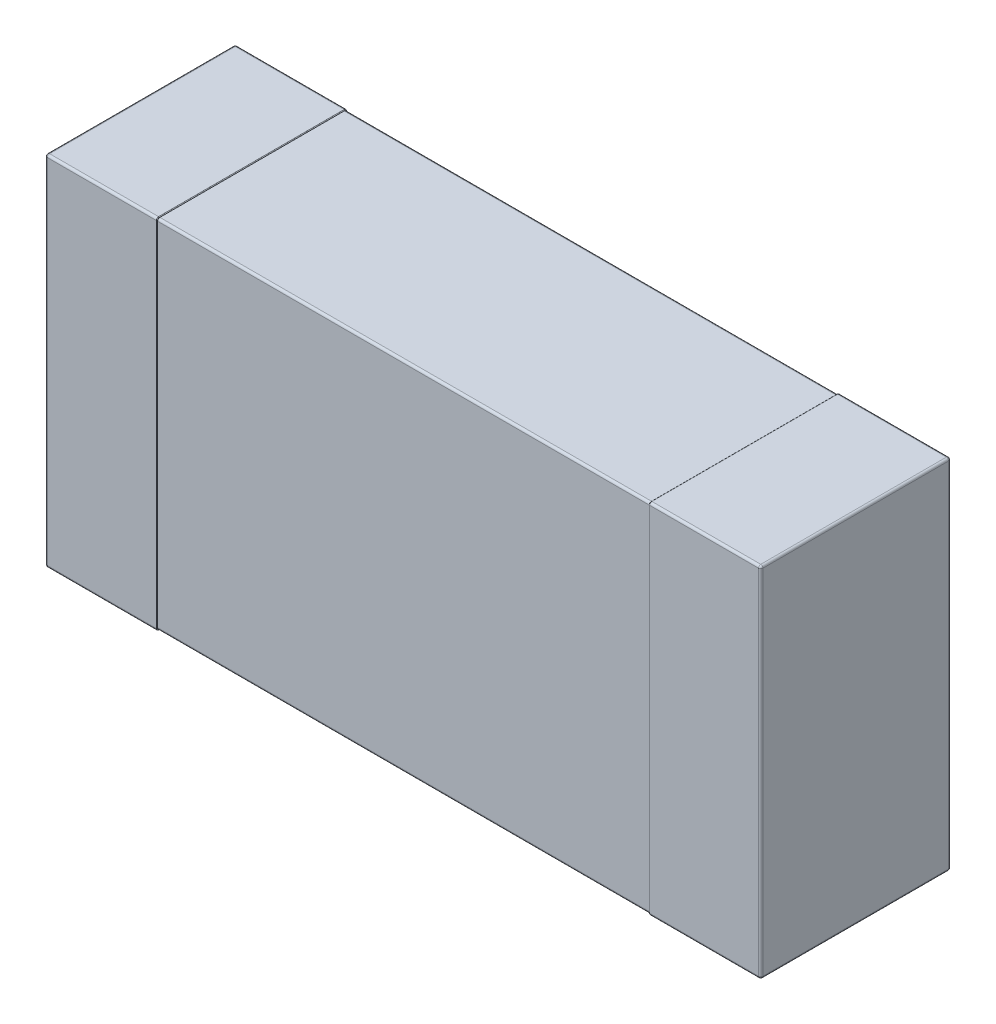
SolidWorks part; units mm, degrees
ref_plane "Top Plane" through (0, 0, 0) normal (0, 0, 1) x (1, 0, 0)
ref_plane "Front Plane" through (0, 0, 0) normal (0, 1, 0) x (1, 0, 0)
ref_plane "Side Plane" through (0, 0, 0) normal (1, 0, 0) x (0, 0, -1)
sketch "Sketch1" plane through (0, 0, 0) normal (0, 0, 1) x (1, 0, 0)
  line L1 (-1.6, 0.8) -> (1.6, 0.8)
  line L2 (-1.6, 0.8) -> (-1.6, -0.8)
  line L3 (-1.6, -0.8) -> (1.6, -0.8)
  line L4 (1.6, 0.8) -> (1.6, -0.8)
  dimension "D1" = 3.2
  dimension "D2" = 1.6
  dimension "D3" = 1.6
  dimension "D4" = 0.8
extrude "All body" add sketch "Sketch1" along normal blind 0.85
sketch "Sketch2" plane through (0, 0, 0) normal (1, 0, 0) x (0, 0, -1)
  line L14 (-0.003, 0.797) -> (-0.847, 0.797)
  line L15 (-0.003, -0.797) -> (-0.003, 0.797)
  line L16 (-0.847, -0.797) -> (-0.003, -0.797)
  line L17 (-0.847, 0.797) -> (-0.847, -0.797)
  line L18 (-0.003, 0.797) -> (-0.847, 0.797)
  line L19 (-0.003, -0.797) -> (-0.003, 0.797)
  line L20 (-0.847, -0.797) -> (-0.003, -0.797)
  line L21 (-0.847, 0.797) -> (-0.847, -0.797)
  dimension "D1" = 0.003
extrude "Cut out the body for pin" cut sketch "Sketch2" against normal blind 1.1 and the other way blind 1.1 flip side to cut
fillet "Body fillet" radius 0.01 4 edges at (0, 0.797, 0.003) (0, 0.797, 0.847) (0, -0.797, 0.003) (0, -0.797, 0.847)
fillet "Pin fillet a" radius 0.01 16 edges at (1.6, -0.8, 0.425) (1.6, 0, 0.85) (1.6, 0.8, 0.425) (1.6, 0, 0) (-1.6, 0.8, 0.425) (-1.6, 0, 0.85) (-1.6, -0.8, 0.425) (-1.6, 0, 0) (1.35, 0.8, 0.85) (1.35, -0.8, 0.85) (1.35, -0.8, 0) (1.35, 0.8, 0) (-1.35, 0.8, 0) (-1.35, -0.8, 0) (-1.35, 0.8, 0.85) (-1.35, -0.8, 0.85)
fillet "Pin fillet b" radius 0.003 16 edges at (1.1, -0.7971, 0.8471) (1.1, -0.8, 0.425) (1.1, -0.7971, 0.0029) (1.1, 0, 0) (1.1, 0.7971, 0.0029) (1.1, 0.8, 0.425) (1.1, 0.7971, 0.8471) (-1.1, -0.7971, 0.8471) (-1.1, -0.8, 0.425) (-1.1, -0.7971, 0.0029) (-1.1, 0, 0) (-1.1, 0.7971, 0.0029) (-1.1, 0.8, 0.425) (-1.1, 0.7971, 0.8471) (1.1, 0, 0.85) (-1.1, 0, 0.85)
